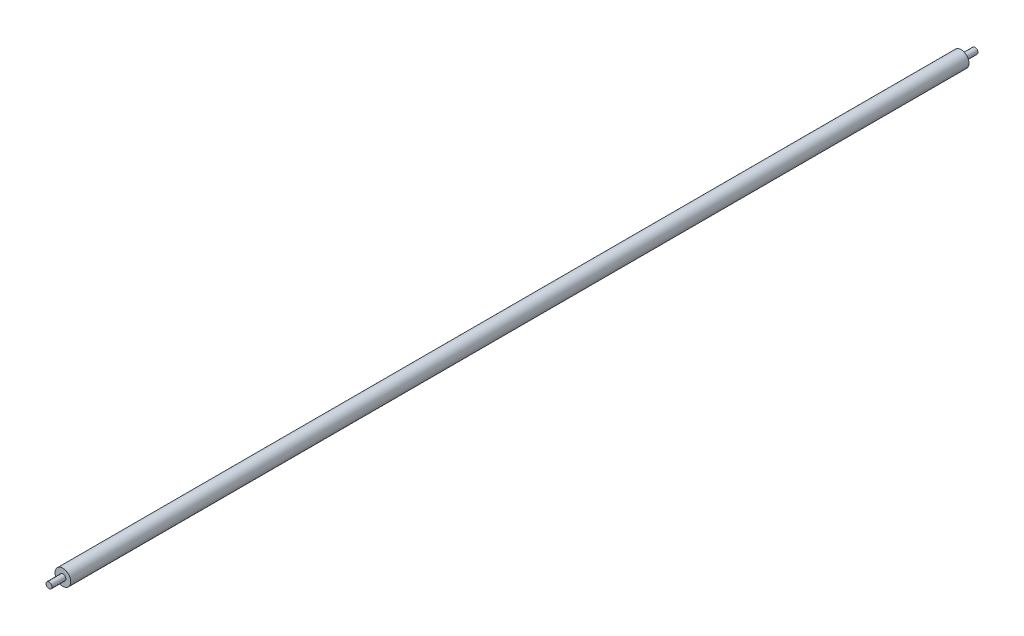
SolidWorks part; units mm, degrees
ref_plane "Front Plane" through (0, 0, 0) normal (0, 0, 1) x (1, 0, 0)
ref_plane "Top Plane" through (0, 0, 0) normal (0, 1, 0) x (1, 0, 0)
ref_plane "Right Plane" through (0, 0, 0) normal (1, 0, 0) x (0, 0, -1)
sketch "Sketch1" plane through (0, 0, 0) normal (0, 0, 1) x (1, 0, 0)
  circle A0 centre (0, 0) radius 0.3219
  circle A1 centre (0, 0) radius 0.85
  dimension "D1" = 0.6438
  dimension "D2" = 1.7
extrude "Boss-Extrude1" add sketch "Sketch1" along normal blind 100 contours A0
extrude "Boss-Extrude2" add sketch "Sketch1<3>" along normal offset from surface (97 mm away) 1.5 from offset 1.5 separate body up to face at (0.3219, 0, 100)
sketch "Sketch1<3>" plane through (0, 0, 0) normal (0, 0, 1) x (1, 0, 0) same geometry as "Sketch1"
